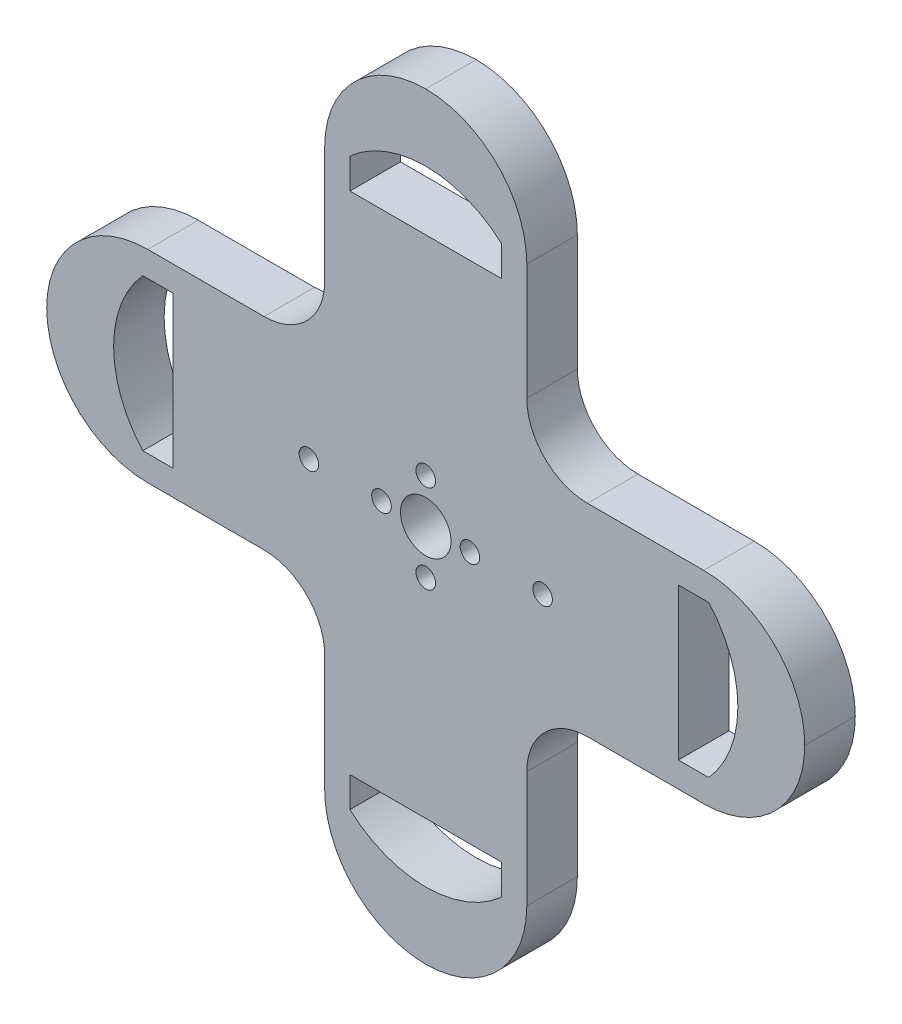
SolidWorks part; units mm, degrees
ref_plane "前视基准面" through (0, 0, 0) normal (0, 0, 1) x (1, 0, 0)
ref_plane "上视基准面" through (0, 0, 0) normal (0, 1, 0) x (1, 0, 0)
ref_plane "右视基准面" through (0, 0, 0) normal (1, 0, 0) x (0, 0, -1)
sketch "草图1" plane through (0, 0, 0) normal (0, 0, 1) x (1, 0, 0)
  line L0 (0, 37.5) -> (0, -37.5) construction
  line L1 (-37.5, 0) -> (37.5, 0) construction
  line L2 (-10, 32.5) -> (-10, 10)
  line L3 (-10, 10) -> (-37.5, 10)
  line L4 (-37.5, 10) -> (-37.5, -10)
  line L5 (-37.5, -10) -> (-10, -10)
  line L6 (-10, -10) -> (-10, -37.5)
  line L7 (-10, -37.5) -> (10, -37.5)
  line L8 (10, -37.5) -> (10, -10)
  line L9 (10, -10) -> (37.5, -10)
  line L10 (37.5, -10) -> (37.5, 10)
  line L11 (37.5, 10) -> (10, 10)
  line L12 (10, 10) -> (10, 32.5)
  line L14 (0, 37.5) -> (10, 37.5)
  line L15 (10, 37.5) -> (10, 32.5)
  line L16 (0, 37.5) -> (-10, 37.5)
  line L17 (-10, 37.5) -> (-10, 32.5)
  dimension "D1" = 37.5
  dimension "D2" = 37.5
  dimension "D3" = 10
  dimension "D4" = 10
extrude "凸台-拉伸1" add sketch "草图1" along normal blind 5
sketch "草图2" plane through (0, 0, 5) normal (0, 0, 1) x (1, 0, 0)
  line L0 (0, 37.5) -> (0, -37.5) construction
  line L1 (10, 37.5) -> (-10, 37.5) construction
  line L2 (-10, -37.5) -> (10, -37.5) construction
  line L3 (-37.5, 0) -> (37.5, 0) construction
  line L4 (-37.5, 10) -> (-37.5, -10) construction
  line L5 (37.5, -10) -> (37.5, 10) construction
  line L6 (-7.5, 25) -> (7.5, 25)
  line L7 (7.5, 25) -> (7.5, 28)
  line L8 (-7.5, 25) -> (-7.5, 28)
  line L9 (-7.5, -25) -> (7.5, -25)
  line L10 (7.5, -25) -> (7.5, -28)
  line L11 (-7.5, -25) -> (-7.5, -28)
  line L12 (-25, 7.5) -> (-25, -7.5)
  line L13 (-25, -7.5) -> (-28, -7.5)
  line L14 (-25, 7.5) -> (-28, 7.5)
  line L15 (7.5, 25) -> (-7.5, 25)
  line L16 (-7.5, 25) -> (-7.5, 28)
  line L17 (7.5, 25) -> (7.5, 28)
  line L18 (25, -7.5) -> (25, 7.5)
  line L19 (25, 7.5) -> (28, 7.5)
  line L20 (25, -7.5) -> (28, -7.5)
  arc A0 (7.5, 28) -> (-7.5, 28) centre (0, 19.6819) ccw
  arc A1 (7.5, -28) -> (-7.5, -28) centre (0, -19.6819) cw
  arc A2 (-28, -7.5) -> (-28, 7.5) centre (-19.6819, 0) cw
  arc A3 (-7.5, 28) -> (7.5, 28) centre (0, 19.6819) cw
  arc A4 (28, 7.5) -> (28, -7.5) centre (19.6819, 0) cw
  point P40 (0, 0)
  dimension "D3" = 11.2
  dimension "D1" = 15
  dimension "D2" = 3
  dimension "D5" = 50
  dimension "D4" = 4
extrude "切除-拉伸1" cut sketch "草图2" against normal through all contours L7 A0 L8 L6 | A2 L13 L12 L14 | A1 L10 L9 L11 | A4 L19 L18 L20 region at (0, 27.5592, 5) region at (0, -27.5592, 5) region at (-27.5592, 0, 5) region at (27.5592, 0, 5)
fillet "圆角1" radius 10 8 edges at (-37.5, 10, 2.5) (-37.5, -10, 2.5) (-10, -37.5, 2.5) (10, -37.5, 2.5) (37.5, -10, 2.5) (37.5, 10, 2.5) (10, 37.5, 2.5) (-10, 37.5, 2.5)
fillet "圆角2" radius 6 4 edges at (-10, -10, 2.5) (10, -10, 2.5) (10, 10, 2.5) (-10, 10, 2.5)
scale "缩放比例1" scale about centroid uniform scaling yes scale factor 1.6
sketch "草图3" plane through (0, 0, 6.5) normal (0, 0, 1) x (1, 0, 0)
  line L0 (-60, 0) -> (60, 0) construction
  line L1 (0, 60) -> (0, -60) construction
  arc A0 (16, 44) -> (0, 60) centre (0, 44) ccw construction
  circle A1 centre (0, 0) radius 4
  circle A2 centre (-7, 0) radius 1.55
  circle A3 centre (7, 0) radius 1.55
  circle A4 centre (0, 7) radius 1.55
  circle A5 centre (0, -7) radius 1.55
  circle A6 centre (-18.5, 0) radius 1.55
  circle A7 centre (18.5, 0) radius 1.55
  dimension "D1" = 8
  dimension "D3" = 3.1
  dimension "D5" = 3.1
  dimension "D7" = 3.1
  dimension "D2" = 7
  dimension "D4" = 7
  dimension "D6" = 11.5
extrude "切除-拉伸2" cut sketch "草图3" against normal through all both and the other way through all
